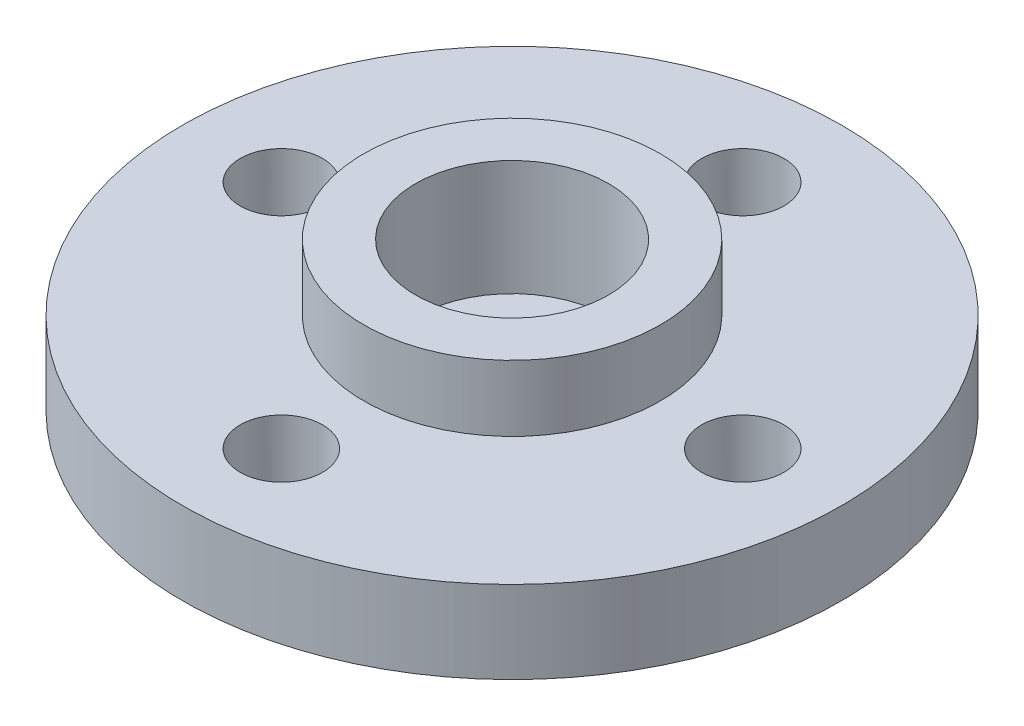
SolidWorks part; units mm, degrees
ref_plane "Front Plane" through (0, 0, 0) normal (0, 0, 1) x (1, 0, 0)
ref_plane "Top Plane" through (0, 0, 0) normal (0, 1, 0) x (1, 0, 0)
ref_plane "Right Plane" through (0, 0, 0) normal (1, 0, 0) x (0, 0, -1)
sketch "Sketch1" plane through (0, 0, 0) normal (1, 0, 0) x (0, 0, -1)
  line L0 (1.6, 0) -> (1.6, 1)
  line L1 (1.6, 1) -> (2.93, 1)
  line L2 (2.93, 1) -> (2.93, 4.5)
  line L3 (2.93, 4.5) -> (4.5, 4.5)
  line L4 (4.5, 4.5) -> (4.5, 2.5)
  line L5 (4.5, 2.5) -> (10, 2.5)
  line L6 (10, 2.5) -> (10, 0)
  line L7 (10, 0) -> (1.6, 0)
  line L8 (0, 0) -> (0, 4.5) construction
  point P11 (0, 0)
  point P12 (1.6, -0.9929)
  dimension "D1" = 3.2
  dimension "D2" = 5.86
  dimension "D3" = 20
  dimension "D4" = 2.5
  dimension "D5" = 4.5
  dimension "D6" = 9
  dimension "D7" = 3.5
revolve "Revolve1" add sketch "Sketch1" angle 360 about L8
hole_wizard "M3 Tapped Hole1" positions "Sketch2" profile "Sketch3" tap size "M3" standard "ISO" end condition through all
sketch "Sketch2" plane through (0, 0, 0) normal (0, -1, 0) x (-1, 0, 0)
  point P0 (0, -7)
  point P4 (0, 0)
  dimension "D1" = 7
sketch "Sketch3" plane through (0, 0, 7) normal (1, 0, 0) x (0, 0, -1)
  line L0 (0, 0) -> (0, 4.5)
  line L1 (0, 4.5) -> (1.25, 4.5)
  line L2 (1.25, 4.5) -> (1.25, 0)
  line L5 (1.25, 0) -> (0, 0)
  line L11 (0, -6.35) -> (0, 107.95) construction
  dimension "Thru Tap Drill Dia." = 2.5
  dimension "Thru Tap Drill Depth" = 4.5
cosmetic thread "Hole Thread1" parameters "D2"=3
pattern_circular "CirPattern1" count 4 over 360 about axis through (0, 0, 0) along (0, -1, 0) of "M3 Tapped Hole1" reverse direction yes
cosmetic thread "Hole Thread2" parameters "D2"=3
cosmetic thread "Hole Thread3" parameters "D2"=3
cosmetic thread "Hole Thread4" parameters "D2"=3
